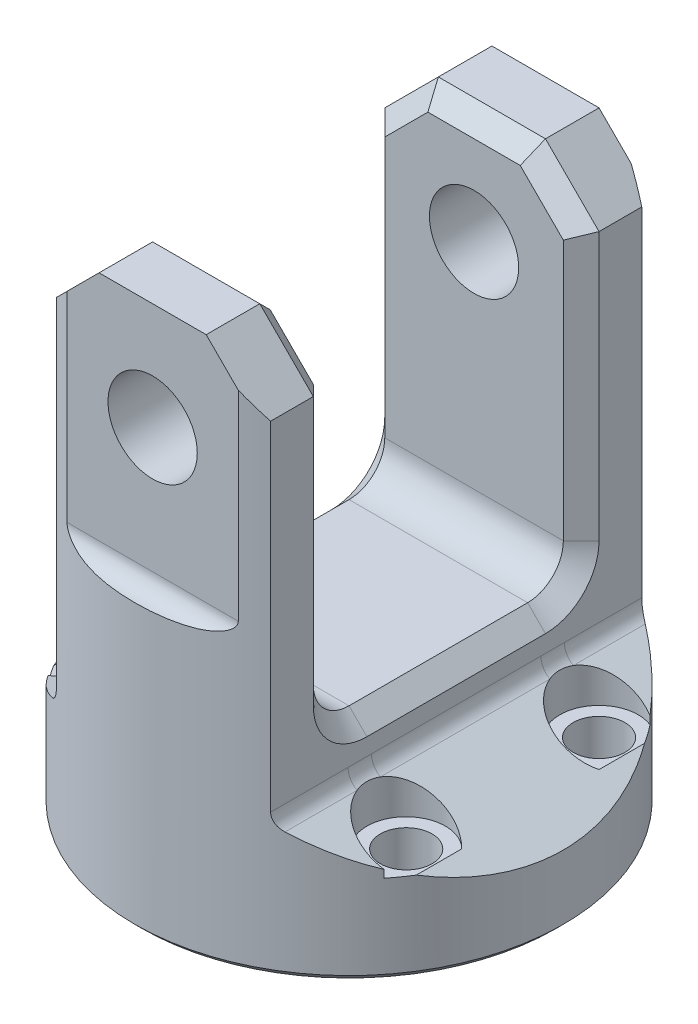
SolidWorks part; units mm, degrees
ref_plane "前基準面" through (0, 0, 0) normal (0, 0, 1) x (1, 0, 0)
ref_plane "上基準面" through (0, 0, 0) normal (0, 1, 0) x (1, 0, 0)
ref_plane "右基準面" through (0, 0, 0) normal (1, 0, 0) x (0, 0, -1)
sketch "草圖1" plane through (0, 0, 0) normal (0, 1, 0) x (1, 0, 0)
  circle A0 centre (0, 0) radius 60
  dimension "D1" = 120
extrude "填料-伸長1" add sketch "草圖1" along normal blind 150
sketch "草圖2" plane through (0, 0, 0) normal (0, 0, 1) x (1, 0, 0)
  line L0 (0, -1000) -> (0, 49000) construction
  line L1 (60, 150) -> (-60, 150) construction
  line L2 (-30, 150) -> (30, 150)
  line L3 (-30, 150) -> (-30, 37.3205)
  line L5 (30, 150) -> (30, 37.3205)
  line L7 (-30, 37.3205) -> (-60, 20)
  line L8 (-60, 150) -> (-60, 0) construction
  line L9 (-60, 20) -> (-60, 0)
  line L10 (-60, 0) -> (60, 0)
  line L11 (60, 0) -> (60, 20)
  line L12 (60, 20) -> (30, 37.3205)
  dimension "D1" = 60
  dimension "D2" = 30
  dimension "D3" = 20
extrude "除料-伸長2" cut sketch "草圖2" against normal mid plane 150 flip side to cut
sketch "草圖3" plane through (-30, 0, 0) normal (-1, 0, 0) x (0, 0, 1)
  line L0 (-51.9615, 150) -> (51.9615, 150) construction
  line L1 (55, 150) -> (60, 150)
  line L2 (55, 150) -> (55, 80)
  line L3 (55, 80) -> (60, 80)
  line L4 (60, 150) -> (60, 80)
  line L5 (60, 0) -> (60, 150) construction
  line L6 (0, -1000) -> (0, 49000) construction
  line L7 (-55, 150) -> (-60, 150)
  line L8 (-55, 150) -> (-55, 80)
  line L9 (-55, 80) -> (-60, 80)
  line L10 (-60, 150) -> (-60, 80)
  line L11 (-60, 0) -> (60, 0) construction
  point P17 (0, 0)
  dimension "D1" = 110
  dimension "D2" = 70
extrude "除料-伸長3" cut sketch "草圖3" against normal through all
sketch "草圖4" plane through (30, 0, 0) normal (1, 0, 0) x (0, 0, -1)
  line L0 (0, -1000) -> (0, 49000) construction
  line L1 (-60, 0) -> (60, 0) construction
  line L2 (-51.9615, 150) -> (51.9615, 150) construction
  line L3 (-35, 150) -> (35, 150)
  line L4 (-35, 150) -> (-35, 50)
  line L5 (-35, 50) -> (35, 50)
  line L6 (35, 150) -> (35, 50)
  point P5 (0, 0)
  dimension "D1" = 70
  dimension "D2" = 50
extrude "除料-伸長4" cut sketch "草圖4" against normal through all
hole_wizard "M27x2.0 螺紋孔1" positions "草圖6" profile "草圖5" tap size "M27x2.0" standard "ISO" end condition through all
sketch "草圖6" plane through (0, 0, 55) normal (0, 0, 1) x (1, 0, 0)
  line L0 (0, -1000) -> (0, 49000) construction
  line L1 (-60, 0) -> (60, 0) construction
  point P0 (0, 120)
  point P7 (0, 0)
  dimension "D1" = 120
sketch "草圖5" plane through (0, 120, 55) normal (1, 0, 0) x (0, -1, 0)
  line L0 (0, 0) -> (0, 115)
  line L1 (0, 115) -> (12.5, 115)
  line L2 (12.5, 115) -> (12.5, 0)
  line L5 (12.5, 0) -> (0, 0)
  line L11 (0, -6.35) -> (0, 107.95) construction
  dimension "貫穿螺孔鑽直徑" = 25
  dimension "貫穿螺孔鑽深度" = 115
cosmetic thread "鑽孔螺紋1" parameters "D2"=27
ref_plane "平面1" through (0, 37.3205, 0) normal (0, -1, 0) x (1, 0, 0)
hole_wizard "M16 六角頭螺栓的柱孔2" positions "草圖10" profile "草圖9" counterbore size "M16" standard "Ansi 公制" end condition through all
sketch "草圖10" plane through (0, 37.3205, 0) normal (0, -1, 0) x (1, 0, 0)
  line L0 (-1000, 0) -> (49000, 0) construction
  line L1 (0, -1000) -> (0, 49000) construction
  point P6 (43, 27)
  point P8 (43, -27)
  point P10 (-43, -27)
  point P12 (-43, 27)
  dimension "D1" = 86
  dimension "D2" = 54
sketch "草圖9" plane through (43, 37.3205, 27) normal (1, 0, 0) x (0, 0, 1)
  line L0 (0, 0) -> (0, 37.3205)
  line L1 (0, 37.3205) -> (7.25, 37.3205)
  line L3 (7.25, 37.3205) -> (7.25, 12)
  line L4 (7.25, 12) -> (11, 12)
  line L5 (11, 12) -> (11, 0)
  line L7 (11, 0) -> (0, 0)
  line L11 (0, -6.35) -> (0, 107.95) construction
  dimension "貫穿孔直徑" = 14.5
  dimension "貫穿孔深度" = 37.3205
  dimension "柱孔直徑" = 22
  dimension "柱孔深度" = 12
chamfer "導角1" distance 15 angle 45 4 edges at (30, 150, 43.4808) (-30, 150, 43.4808) (-30, 150, -43.4808) (30, 150, -43.4808)
fillet "圓角1" radius 10 2 edges at (0, 50, 35) (0, 50, -35)
chamfer "導角2" distance 5 angle 45 16 edges at (30, 97.5, -35) (30, 52.9289, -32.0711) (30, 50, 0) (30, 52.9289, 32.0711) (30, 97.5, 35) (22.5, 142.5, 35) (0, 150, 35) (-22.5, 142.5, 35) (-30, 97.5, 35) (-30, 52.9289, 32.0711) (-30, 50, 0) (-30, 52.9289, -32.0711) (22.5, 142.5, -35) (-30, 97.5, -35) (-22.5, 142.5, -35) (0, 150, -35)
fillet "圓角2" radius 5 2 edges at (0, 80, 55) (0, 80, -55)
fillet "圓角3" radius 5 2 edges at (30, 37.3205, 0) (-30, 37.3205, 0)
chamfer "導角3" distance 2 angle 45 1 edges at (0, 0, 60)
